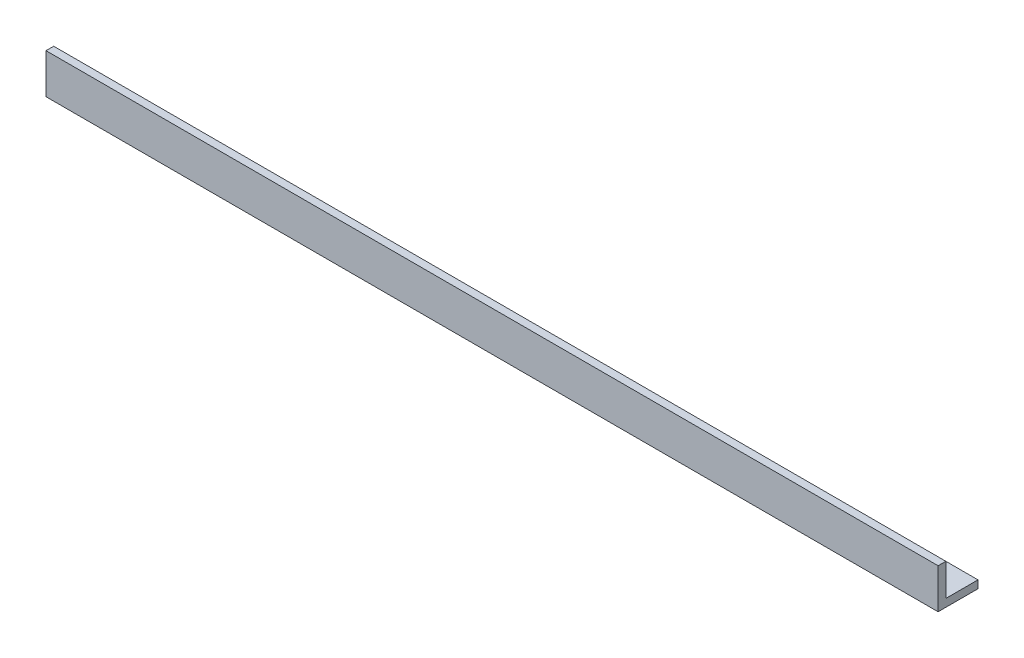
SolidWorks part; units mm, degrees
ref_plane "Front Plane" through (0, 0, 0) normal (0, 0, 1) x (1, 0, 0)
ref_plane "Top Plane" through (0, 0, 0) normal (0, 1, 0) x (1, 0, 0)
ref_plane "Right Plane" through (0, 0, 0) normal (1, 0, 0) x (0, 0, -1)
sketch "Sketch1" plane through (0, 0, 0) normal (1, 0, 0) x (0, 0, -1)
  line L0 (0, 0) -> (0, 19.05)
  line L1 (0, 19.05) -> (3.685, 19.05)
  line L2 (3.685, 19.05) -> (3.685, 3.685)
  line L3 (3.685, 3.685) -> (19.05, 3.685)
  line L4 (19.05, 3.685) -> (19.05, 0)
  line L5 (19.05, 0) -> (0, 0)
extrude "Boss-Extrude1" add sketch "Sketch1" along normal blind 426
